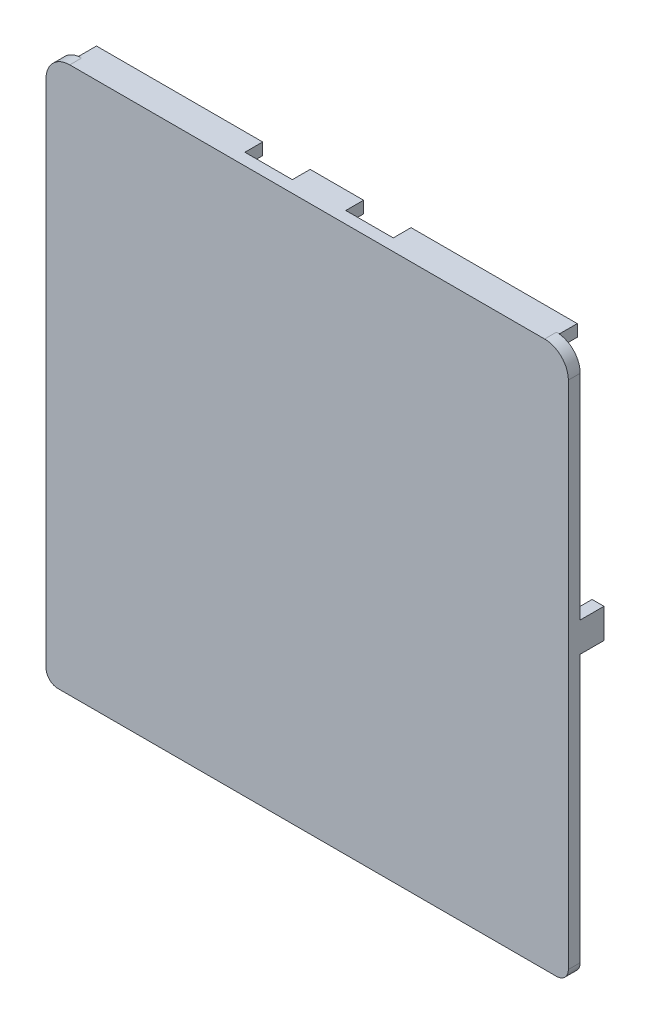
SolidWorks part; units mm, degrees
ref_plane "Front Plane" through (0, 0, 0) normal (0, 0, 1) x (1, 0, 0)
ref_plane "Top Plane" through (0, 0, 0) normal (0, 1, 0) x (1, 0, 0)
ref_plane "Right Plane" through (0, 0, 0) normal (1, 0, 0) x (0, 0, -1)
sketch "Sketch1" plane through (0, 0, 0) normal (0, 0, 1) x (1, 0, 0)
  line L1 (-73.8547, 63.883) -> (14.1453, 63.883)
  line L2 (-73.8547, 63.883) -> (-73.8547, -28.117)
  line L3 (-73.8547, -28.117) -> (14.1453, -28.117)
  line L4 (14.1453, 63.883) -> (14.1453, -28.117)
  dimension "D1" = 88
  dimension "D2" = 92
extrude "Boss-Extrude1" add sketch "Sketch1" along normal blind 2
fillet "Fillet1" radius 4 2 edges at (-73.8547, 63.883, 1) (14.1453, 63.883, 1)
sketch "Sketch3" plane through (0, 0, 0) normal (0, 0, -1) x (-1, 0, 0)
  line L0 (-10.1453, 63.883) -> (69.8547, 63.883) construction
  line L1 (70.3547, 63.883) -> (42.3547, 63.883)
  line L2 (70.3547, 63.883) -> (70.3547, 61.883)
  line L3 (70.3547, 61.883) -> (42.3547, 61.883)
  line L4 (42.3547, 63.883) -> (42.3547, 61.883)
  line L5 (73.8547, 59.883) -> (73.8547, -28.117) construction
  line L6 (34.3547, 63.883) -> (25.3547, 63.883)
  line L7 (34.3547, 63.883) -> (34.3547, 61.883)
  line L8 (34.3547, 61.883) -> (25.3547, 61.883)
  line L9 (25.3547, 63.883) -> (25.3547, 61.883)
  line L10 (17.3547, 63.883) -> (-10.6453, 63.883)
  line L11 (17.3547, 63.883) -> (17.3547, 61.883)
  line L12 (17.3547, 61.883) -> (-10.6453, 61.883)
  line L13 (-10.6453, 63.883) -> (-10.6453, 61.883)
  line L14 (-14.1453, -28.117) -> (-14.1453, 59.883) construction
  dimension "D1" = 2
  dimension "D2" = 2
  dimension "D3" = 2
  dimension "D4" = 28
  dimension "D5" = 9
  dimension "D6" = 28
  dimension "D7" = 8
  dimension "D8" = 8
  dimension "D9" = 3.5
  dimension "D10" = 3.5
extrude "Boss-Extrude3" add sketch "Sketch3" along normal blind 3
sketch "Sketch4" plane through (0, 0, 0) normal (0, 0, -1) x (-1, 0, 0)
  line L0 (-14.1453, -28.117) -> (-14.1453, 59.883) construction
  line L1 (-12.1453, 18.883) -> (-14.1453, 18.883)
  line L2 (-12.1453, 18.883) -> (-12.1453, 23.883)
  line L3 (-12.1453, 23.883) -> (-14.1453, 23.883)
  line L4 (-14.1453, 18.883) -> (-14.1453, 23.883)
  line L5 (-12.1453, 23.883) -> (-14.1453, 23.883) construction
  point P7 (-13.1453, 23.883)
  dimension "D1" = 0
extrude "Boss-Extrude4" add sketch "Sketch4" along normal blind 4
fillet "Fillet2" radius 2 2 edges at (14.1453, -28.117, 1) (-73.8547, -28.117, 1)
sketch "Sketch5" plane through (0, 0, 0) normal (0, 0, -1) x (-1, 0, 0)
  line L0 (73.8547, 59.883) -> (73.8547, -26.117) construction
  line L1 (71.8547, -26.117) -> (68.8547, -26.117)
  line L2 (71.8547, -26.117) -> (71.8547, 54.7492)
  line L3 (71.8547, 54.7492) -> (68.8547, 54.7492)
  line L5 (68.8547, -26.117) -> (-12.1453, -26.117)
  line L7 (68.8547, -23.117) -> (-9.1453, -23.117)
  line L8 (-12.1453, -26.117) -> (-12.1453, -23.117)
  line L10 (-12.1453, -23.117) -> (-12.1453, 54.89)
  line L11 (-12.1453, 54.89) -> (-9.1453, 54.89)
  line L12 (-9.1453, -23.117) -> (-9.1453, 54.89)
  line L13 (71.8547, -28.117) -> (-12.1453, -28.117) construction
  line L14 (-14.1453, -26.117) -> (-14.1453, 18.883) construction
  line L16 (68.8547, -23.117) -> (68.8547, 54.7492)
  point P16 (0, 0)
  point P18 (71.3289, -19.4356)
  dimension "D1" = 3
  dimension "D2" = 3
  dimension "D3" = 3
  dimension "D4" = 2
  dimension "D5" = 2
  dimension "D6" = 2
extrude "Boss-Extrude5" add sketch "Sketch5" along normal blind 2
fillet "Fillet4" radius 0.5 4 edges at (-71.8547, 14.3161, -2) (-29.8547, -26.117, -2) (12.1453, -3.617, -2) (12.1453, 39.3865, -2)
